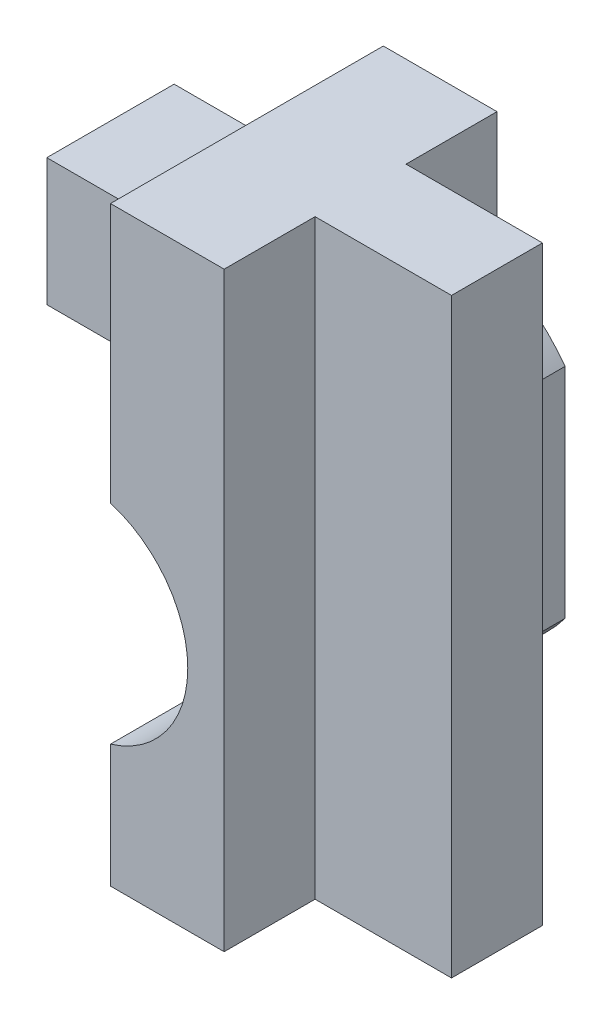
SolidWorks part; units mm, degrees
note: The reader was unsure of these and kept them because the rebuilt part matched: shared geometry of "Sketch17<2>".
ref_plane "Front Plane" through (0, 0, 0) normal (0, 0, 1) x (1, 0, 0)
ref_plane "Top Plane" through (0, 0, 0) normal (0, 1, 0) x (1, 0, 0)
ref_plane "Right Plane" through (0, 0, 0) normal (1, 0, 0) x (0, 0, -1)
sketch "Sketch1" plane through (0, 0, 0) normal (0, 0, 1) x (1, 0, 0)
  line L0 (-11.5, 0) -> (11.5, 0) construction
  line L1 (3.75, -5) -> (14.7, -5)
  line L2 (-14.7, -5) -> (-3.75, -5)
  line L3 (-14.7, -5) -> (-14.7, 8)
  line L4 (-14.7, 8) -> (14.7, 8)
  line L5 (14.7, -5) -> (14.7, 8)
  line L6 (-17.6832, -10.5909) -> (24.7009, -10.5909)
  line L7 (-24.9768, -7) -> (25.0232, -7) construction
  line L8 (-24.9768, -7) -> (-24.9768, -5) construction
  line L9 (-24.9768, -5) -> (-3.75, -5) construction
  line L10 (25.0232, -7) -> (25.0232, -5) construction
  line L11 (-24.9768, -7) -> (25.0232, -5) construction
  line L12 (-24.9768, -5) -> (25.0232, -7) construction
  line L13 (-5.1, -3.6128) -> (-5.1, 3.6128)
  line L14 (9, -3) -> (14, -3) construction
  line L15 (9, -3) -> (9, 3) construction
  line L16 (9, 3) -> (14, 3) construction
  line L17 (14, -3) -> (14, 3) construction
  line L18 (9, -3) -> (14, 3) construction
  line L19 (9, 3) -> (14, -3) construction
  line L20 (5.1, -3.6128) -> (5.1, 3.6128)
  line L21 (-5.1, -3.6128) -> (5.1, 3.6128) construction
  line L22 (-5.1, 3.6128) -> (5.1, -3.6128) construction
  line L23 (3.75, -5) -> (25.0232, -5) construction
  circle A0 centre (0, 0) radius 2 construction
  circle A1 centre (11.5, 0) radius 9.5 construction
  circle A2 centre (-11.5, 0) radius 9.5 construction
  circle A3 centre (11.5, 0) radius 10.5909 construction
  circle A4 centre (-11.5, 0) radius 10.5909 construction
  circle A5 centre (0, 0) radius 0.5
  circle A6 centre (-11.5, 0) radius 1
  circle A7 centre (11.5, 0) radius 1
  arc A8 (5.1, 3.6128) -> (-5.1, 3.6128) centre (0, 0) ccw
  arc A9 (-5.1, -3.6128) -> (-3.75, -5) centre (0, 0) ccw
  arc A10 (3.75, -5) -> (5.1, -3.6128) centre (0, 0) ccw
  point P13 (0, 0)
  point P17 (0, 8)
  point P18 (0.0232, -6)
  point P29 (3.5089, -10.5909)
  dimension "D1" = 4
  dimension "D2" = 19
  dimension "D5" = 1
  dimension "D6" = 2
  dimension "D9" = 12.5
  dimension "D3" = 13
  dimension "D4" = 2
  dimension "D7" = 5
  dimension "D8" = 6
  dimension "D10" = 10.2
  dimension "D11" = 8
  dimension "D12" = 3.2
extrude "Boss-Extrude1" add sketch "Sketch1" along normal blind 6 contours A10 L1 L5 L4 L3 L2 A9 L13 A8 L20 A7 A6
sketch "Sketch2" plane through (0, 0, 0) normal (0, 0, 1) x (1, 0, 0)
  circle A0 centre (-11.5, 0) radius 2.6
  circle A1 centre (11.5, 0) radius 2.6
  dimension "D1" = 5.2
extrude "Cut-Extrude1" cut sketch "Sketch2" along normal blind 6
sketch "Sketch3" plane through (0, 0, 0) normal (0, 0, 1) x (1, 0, 0)
  line L0 (-14.7, -5) -> (-3.75, -5) construction
  line L1 (-14.7, 8) -> (-22.3, 8)
  line L2 (-14.7, 8) -> (-14.7, -5)
  line L3 (-14.7, -5) -> (-22.3, -5)
  line L4 (-22.3, 8) -> (-22.3, -5)
  dimension "D1" = 7.6
extrude "Boss-Extrude2" add sketch "Sketch3" along normal blind 6
sketch "Sketch6" plane through (0, 0, 0) normal (0, 1, 0) x (1, 0, 0)
  line L0 (-22.3, -6) -> (-22.3, 0) construction
  line L1 (-22.3, -2) -> (-25.3, -2)
  line L2 (-22.3, -2) -> (-22.3, -4)
  line L3 (-22.3, -4) -> (-25.3, -4)
  line L4 (-25.3, -2) -> (-25.3, -4)
  line L5 (14.7, -6) -> (14.7, 0) construction
  line L6 (14.7, -2) -> (17.7, -2)
  line L7 (14.7, -2) -> (14.7, -4)
  line L8 (14.7, -4) -> (17.7, -4)
  line L9 (17.7, -2) -> (17.7, -4)
  point P12 (-22.3, -3)
  point P13 (-22.3, -3)
  dimension "D1" = 2
  dimension "D2" = 3
extrude "Boss-Extrude5" add sketch "Sketch6" along normal up to surface (13 mm away) from surface
sketch "Sketch10" plane through (0, 0, 6) normal (0, 0, 1) x (1, 0, 0)
  line L0 (14.7, 2.4) -> (14.7, -2.4)
  line L2 (14.7, -5) -> (14.7, 8) construction
  circle A0 centre (-11.5, 0) radius 2.6
  circle A1 centre (11.5, 0) radius 2.6
  circle A2 centre (-11.5, 0) radius 2.6 construction
  circle A3 centre (11.5, 0) radius 2.6 construction
  arc A4 (14.7, 2.4) -> (14.7, -2.4) centre (11.5, 0) ccw
  circle A5 centre (-11.5, 0) radius 4
  dimension "D1" = 8
extrude "Boss-Extrude6" add sketch "Sketch10" against normal blind 1.5 from surface at -6 starting at face at (-8.9, 0, 0)
sketch "Sketch12" plane through (0, 0, 0) normal (0, 0, -1) x (-1, 0, 0)
  circle A0 centre (-11.5, 0) radius 2.4
  circle A1 centre (11.5, 0) radius 2.4
  circle A2 centre (11.5, 0) radius 2.6
  circle A3 centre (-11.5, 0) radius 2.6
  circle A4 centre (-11.5, 0) radius 2.6 construction
  circle A5 centre (11.5, 0) radius 2.6 construction
  dimension "D1" = 4.8
extrude "Boss-Extrude7" add sketch "Sketch12" along normal blind 2 from surface at -6 starting at face at (-8.9, 0, 6)
sketch "Sketch13" plane through (0, -5, 0) normal (0, -1, 0) x (1, 0, 0)
  line L12 (-22.3, 6) -> (-3.75, 6) construction
  line L13 (-22.3, 0) -> (-16.3, 0)
  line L14 (-22.3, 0) -> (-22.3, 2)
  line L15 (-22.3, 2) -> (-20.8, 2)
  line L16 (-16.3, 0) -> (-16.3, 2)
  line L18 (-20.8, 2) -> (-20.8, 6)
  line L19 (-20.8, 6) -> (-17.8, 6)
  line L20 (-17.8, 2) -> (-17.8, 6)
  line L21 (-17.8, 2) -> (-16.3, 2)
  dimension "D1" = 6
  dimension "D2" = 3
  dimension "D3" = 2
extrude "Cut-Extrude2" cut sketch "Sketch13" against normal blind 7
sketch "Sketch14" plane through (0, 0, 0) normal (0, 0, -1) x (-1, 0, 0)
  line L0 (22.3, 8) -> (-14.7, 8) construction
  line L1 (20.8, 2) -> (17.8, 2)
  line L2 (20.8, 2) -> (20.8, 8)
  line L3 (20.8, 8) -> (17.8, 8)
  line L4 (17.8, 2) -> (17.8, 8)
  line L5 (17.8, 2) -> (17.8, -5) construction
extrude "Cut-Extrude3" cut sketch "Sketch14" against normal blind 2
sketch "Sketch15" plane through (0, 0, 0) normal (0, 0, 1) x (1, 0, 0)
  line L0 (-17.8, 8) -> (14.7, 8) construction
  line L1 (-12, -5) -> (-12.2, -5)
  line L2 (-12, -5) -> (-12, 8)
  line L3 (-12, 8) -> (-12.2, 8)
  line L4 (-12.2, -5) -> (-12.2, 8)
  line L5 (-12, -5) -> (-12.2, 8) construction
  line L6 (-12, 8) -> (-12.2, -5) construction
  line L7 (3.75, -5) -> (14.7, -5) construction
  line L8 (12, -5) -> (12.2, -5)
  line L9 (12, -5) -> (12, 8)
  line L10 (12, 8) -> (12.2, 8)
  line L11 (12.2, -5) -> (12.2, 8)
  line L12 (12, -5) -> (12.2, 8) construction
  line L13 (12, 8) -> (12.2, -5) construction
  circle A0 centre (-11.5, 0) radius 2.4 construction
  circle A1 centre (11.5, 0) radius 2.4 construction
  point P0 (-12.1, 1.5)
  point P7 (12.1, 1.5)
  dimension "D1" = 0.2
  dimension "D2" = 0.5
  dimension "D3" = 0.5
extrude "Cut-Extrude5" cut sketch "Sketch15" against normal mid plane 15
sketch "Sketch16" plane through (12, 0, 0) normal (1, 0, 0) x (0, 0, -1)
  line L0 (0, 8) -> (-6, 2.3473) construction
  line L2 (-1.5, 3.6737) -> (-4.5, 3.6737)
  line L3 (-1.5, 3.6737) -> (-1.5, 6.6737)
  line L4 (-1.5, 6.6737) -> (-4.5, 6.6737)
  line L5 (-4.5, 3.6737) -> (-4.5, 6.6737)
  line L6 (-1.5, 3.6737) -> (-4.5, 6.6737) construction
  line L7 (-1.5, 6.6737) -> (-4.5, 3.6737) construction
  point P4 (-3, 5.1737)
  dimension "D1" = 3
extrude "Cut-Extrude6" cut sketch "Sketch16" against normal blind 3
mirror "Mirror1" about plane through (0, 0, 0) normal (1, 0, 0) of "Cut-Extrude6"
sketch "Sketch17" plane through (-12.2, 0, 0) normal (1, 0, 0) x (0, 0, -1)
  line L0 (-4.5, 6.6737) -> (-1.5, 3.6737) construction
  line L2 (-4.4, 3.7737) -> (-1.6, 3.7737)
  line L3 (-4.4, 3.7737) -> (-4.4, 6.5737)
  line L4 (-4.4, 6.5737) -> (-1.6, 6.5737)
  line L5 (-1.6, 3.7737) -> (-1.6, 6.5737)
  line L6 (-4.4, 3.7737) -> (-1.6, 6.5737) construction
  line L7 (-4.4, 6.5737) -> (-1.6, 3.7737) construction
  point P4 (-3, 5.1737)
  dimension "D1" = 2.8
extrude "Boss-Extrude9" add sketch "Sketch17" along normal blind 3
extrude "Boss-Extrude10" add sketch "Sketch17<2>" against normal blind 3 from surface at 24.4 starting at face at (12.2, 4.1845, 2.125)
sketch "Sketch17<2>" plane through (-12.2, 0, 0) normal (1, 0, 0) x (0, 0, -1) same geometry as "Sketch17"
sketch "Sketch18" plane through (0, 0, 0) normal (0, 0, 1) x (1, 0, 0)
  line L5 (12, 8) -> (-25.3, 8)
  line L6 (12, 8) -> (12, -5)
  line L7 (12, -5) -> (-25.3, -5)
  line L8 (-25.3, 8) -> (-25.3, -5)
  point P0 (0, 0)
extrude "Cut-Extrude11" cut sketch "Sketch18" against normal mid plane 18
sketch "Sketch20" plane through (12.2, 0, 0) normal (-1, 0, 0) x (0, 0, 1)
  line L1 (1.6, 6.5737) -> (4.4, 6.5737)
  line L2 (1.6, 6.5737) -> (1.6, 3.7737)
  line L3 (1.6, 3.7737) -> (4.4, 3.7737)
  line L4 (4.4, 6.5737) -> (4.4, 3.7737)
extrude "Boss-Extrude11" add sketch "Sketch20" along normal blind 3
